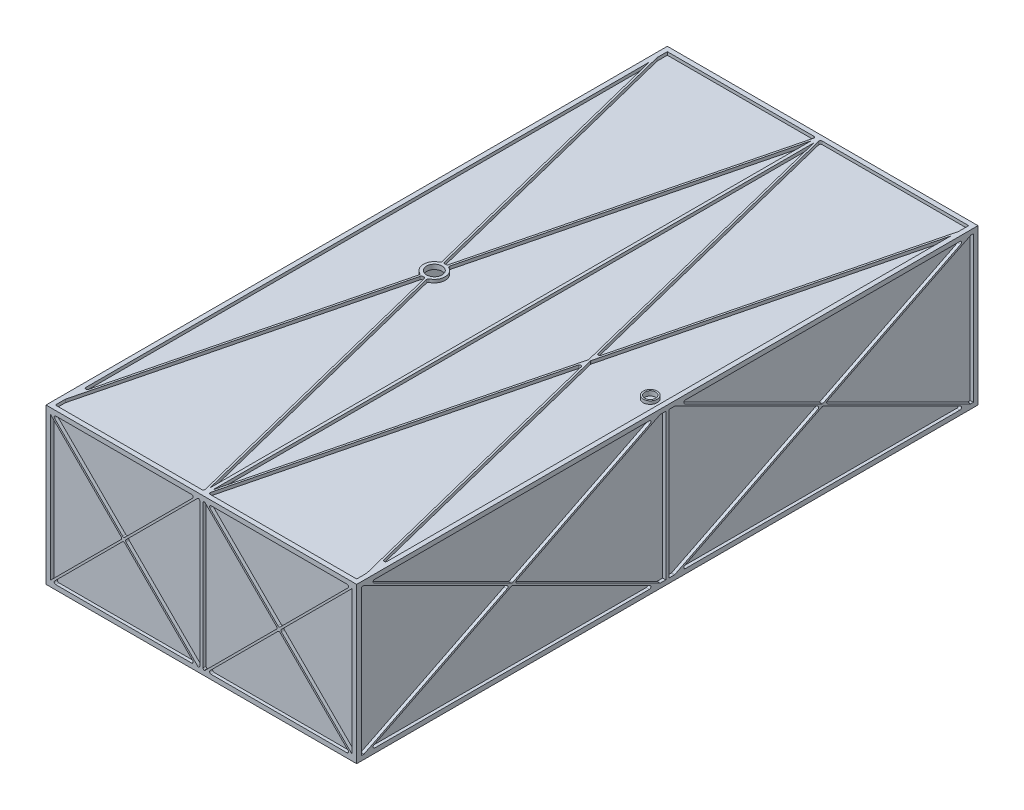
SolidWorks part; units mm, degrees
ref_plane "Front Plane" through (0, 0, 0) normal (0, 0, 1) x (1, 0, 0)
ref_plane "Top Plane" through (0, 0, 0) normal (0, 1, 0) x (1, 0, 0)
ref_plane "Right Plane" through (0, 0, 0) normal (1, 0, 0) x (0, 0, -1)
sketch "Sketch1" plane through (0, 0, 0) normal (0, 1, 0) x (1, 0, 0)
  line L1 (-500, 1000) -> (500, 1000)
  line L2 (-500, 1000) -> (-500, -1000)
  line L3 (-500, -1000) -> (500, -1000)
  line L4 (500, 1000) -> (500, -1000)
  line L5 (-500, 1000) -> (500, -1000) construction
  line L6 (-500, -1000) -> (500, 1000) construction
  point P0 (0, 0)
  dimension "D1" = 2000
  dimension "D2" = 1000
extrude "Boss-Extrude1" add sketch "Sketch1" along normal blind 500
sketch "Sketch2" plane through (0, 0, 1000) normal (0, 0, 1) x (1, 0, 0)
  line L0 (485, 485) -> (-485, 485)
  line L1 (-485, 485) -> (-485, 15)
  line L2 (-485, 15) -> (485, 15)
  line L3 (485, 15) -> (485, 485)
  line L4 (-500, 0) -> (500, 0)
  line L5 (500, 0) -> (500, 500)
  line L6 (500, 500) -> (-500, 500)
  line L7 (-500, 500) -> (-500, 0)
  line L8 (-500, 0) -> (500, 0) construction
  line L9 (500, 0) -> (500, 500) construction
  line L10 (500, 500) -> (-500, 500) construction
  line L11 (-500, 500) -> (-500, 0) construction
  dimension "D1" = 0
  dimension "D2" = 15
extrude "Cut-Extrude1" cut sketch "Sketch2" against normal through all contours L0 L1 L2 L3
sketch "Sketch3" plane through (-500, 0, 0) normal (-1, 0, 0) x (0, 0, 1)
  line L0 (-985, 15) -> (985, 15)
  line L1 (985, 15) -> (985, 485)
  line L2 (985, 485) -> (-985, 485)
  line L3 (-985, 485) -> (-985, 15)
  line L4 (-1000, 0) -> (1000, 0)
  line L5 (1000, 0) -> (1000, 500)
  line L6 (1000, 500) -> (-1000, 500)
  line L7 (-1000, 500) -> (-1000, 0)
  line L8 (-1000, 0) -> (1000, 0) construction
  line L9 (1000, 0) -> (1000, 500) construction
  line L10 (1000, 500) -> (-1000, 500) construction
  line L11 (-1000, 500) -> (-1000, 0) construction
  dimension "D1" = 0
  dimension "D2" = 15
extrude "Cut-Extrude2" cut sketch "Sketch3" against normal through all
sketch "Sketch4" plane through (0, 500, 0) normal (0, 1, 0) x (1, 0, 0)
  line L0 (485, -985) -> (485, 985)
  line L1 (485, 985) -> (-485, 985)
  line L2 (-485, 985) -> (-485, -985)
  line L3 (-485, -985) -> (485, -985)
  line L4 (500, -1000) -> (500, 1000)
  line L5 (500, 1000) -> (-500, 1000)
  line L6 (-500, 1000) -> (-500, -1000)
  line L7 (-500, -1000) -> (500, -1000)
  line L8 (500, -1000) -> (500, 1000) construction
  line L9 (500, 1000) -> (-500, 1000) construction
  line L10 (-500, 1000) -> (-500, -1000) construction
  line L11 (-500, -1000) -> (500, -1000) construction
  dimension "D1" = 0
  dimension "D2" = 15
extrude "Cut-Extrude3" cut sketch "Sketch4" against normal through all
sketch "Sketch8" plane through (0, 485, 0) normal (0, -1, 0) x (1, 0, 0)
  line L0 (485, 985) -> (485, -985) construction
  line L1 (485, -985) -> (-485, -985) construction
  line L2 (-485, -985) -> (-485, 985) construction
  line L3 (-485, 985) -> (485, 985) construction
  line L4 (485, 985) -> (485, -985)
  line L5 (485, -985) -> (-485, -985)
  line L6 (-485, -985) -> (-485, 985)
  line L7 (-485, 985) -> (485, 985)
extrude "Boss-Extrude3" add sketch "Sketch8" against normal blind 5
sketch "Sketch9" plane through (0, 15, 0) normal (0, 1, 0) x (1, 0, 0)
  line L0 (-485, 985) -> (485, 985) construction
  line L1 (485, 985) -> (485, -985) construction
  line L2 (-485, -985) -> (-485, 985) construction
  line L3 (485, -985) -> (-485, -985) construction
  line L4 (-485, 985) -> (485, 985)
  line L5 (485, 985) -> (485, -985)
  line L6 (-485, -985) -> (-485, 985)
  line L7 (485, -985) -> (-485, -985)
extrude "Boss-Extrude4" add sketch "Sketch9" against normal blind 5
sketch "Sketch10" plane through (0, 0, -985) normal (0, 0, 1) x (1, 0, 0)
  line L0 (485, 15) -> (485, 485) construction
  line L1 (-485, 15) -> (485, 15) construction
  line L2 (-485, 485) -> (-485, 15) construction
  line L3 (485, 485) -> (-485, 485) construction
  line L4 (485, 15) -> (485, 485)
  line L5 (-485, 15) -> (485, 15)
  line L6 (-485, 485) -> (-485, 15)
  line L7 (485, 485) -> (-485, 485)
extrude "Boss-Extrude5" add sketch "Sketch10" against normal blind 5
sketch "Sketch11" plane through (0, 0, 985) normal (0, 0, -1) x (-1, 0, 0)
  line L4 (-485, 15) -> (485, 15)
  line L5 (485, 15) -> (485, 485)
  line L6 (485, 485) -> (-485, 485)
  line L7 (-485, 485) -> (-485, 15)
  line L8 (-485, 15) -> (485, 15)
  line L9 (485, 15) -> (485, 485)
  line L10 (485, 485) -> (-485, 485)
  line L11 (-485, 485) -> (-485, 15)
  dimension "D1" = 0
extrude "Boss-Extrude6" add sketch "Sketch11" against normal blind 5
sketch "Sketch12" plane through (-485, 0, 0) normal (1, 0, 0) x (0, 0, -1)
  line L0 (985, 485) -> (985, 15) construction
  line L1 (985, 15) -> (-985, 15) construction
  line L2 (-985, 15) -> (-985, 485) construction
  line L3 (-985, 485) -> (985, 485) construction
  line L4 (985, 485) -> (985, 15)
  line L5 (985, 15) -> (-985, 15)
  line L6 (-985, 15) -> (-985, 485)
  line L7 (-985, 485) -> (985, 485)
extrude "Boss-Extrude7" add sketch "Sketch12" against normal blind 5
sketch "Sketch13" plane through (485, 0, 0) normal (-1, 0, 0) x (0, 0, 1)
  line L4 (985, 485) -> (-985, 485)
  line L5 (-985, 485) -> (-985, 15)
  line L6 (-985, 15) -> (985, 15)
  line L7 (985, 15) -> (985, 485)
  line L8 (985, 485) -> (-985, 485)
  line L9 (-985, 485) -> (-985, 15)
  line L10 (-985, 15) -> (985, 15)
  line L11 (985, 15) -> (985, 485)
  dimension "D1" = 0
extrude "Boss-Extrude8" add sketch "Sketch13" against normal blind 5
sketch "Sketch14" plane through (0, 0, -990) normal (0, 0, -1) x (-1, 0, 0)
  line L0 (-500, 500) -> (0, 0) construction
  line L1 (0, 0) -> (500, 500) construction
  line L2 (-500, 0) -> (0, 500) construction
  line L3 (0, 500) -> (500, 0) construction
  line L4 (-500, 0) -> (500, 0)
  line L5 (500, 0) -> (500, 500)
  line L6 (500, 500) -> (-500, 500)
  line L7 (-500, 500) -> (-500, 0)
  line L8 (-500, 0) -> (500, 0) construction
  line L9 (500, 0) -> (500, 500) construction
  line L10 (500, 500) -> (-500, 500) construction
  line L11 (-500, 500) -> (-500, 0) construction
  line L12 (-495.7574, 0) -> (-250, 245.7574)
  line L13 (5, 490.7574) -> (245.7574, 250)
  line L14 (-500, 495.7574) -> (-254.2426, 250)
  line L15 (4.2426, 0) -> (250, 245.7574)
  line L16 (-500, 4.2426) -> (-254.2426, 250)
  line L17 (4.2426, 500) -> (250, 254.2426)
  line L18 (-495.7574, 500) -> (-250, 254.2426)
  line L19 (5, 9.2426) -> (245.7574, 250)
  line L20 (-497.8787, 502.1213) -> (0, 4.2426) construction
  line L21 (-502.1213, 497.8787) -> (0, -4.2426) construction
  line L22 (-502.1213, 2.1213) -> (0, 504.2426) construction
  line L23 (-497.8787, -2.1213) -> (0, 495.7574) construction
  line L24 (0, -4.2426) -> (502.1213, 497.8787) construction
  line L25 (0, 504.2426) -> (502.1213, 2.1213) construction
  line L26 (0, 495.7574) -> (497.8787, -2.1213) construction
  line L27 (0, 4.2426) -> (497.8787, 502.1213) construction
  line L28 (-250, 254.2426) -> (-4.2426, 500)
  line L29 (-245.7574, 250) -> (-5, 490.7574)
  line L30 (-250, 245.7574) -> (-4.2426, 0)
  line L31 (-245.7574, 250) -> (-5, 9.2426)
  line L32 (250, 254.2426) -> (495.7574, 500)
  line L33 (254.2426, 250) -> (500, 495.7574)
  line L34 (254.2426, 250) -> (500, 4.2426)
  line L35 (250, 245.7574) -> (495.7574, 0)
  line L36 (-500, 4.2426) -> (-500, 0)
  line L37 (-500, 0) -> (-495.7574, 0)
  line L38 (-4.2426, 0) -> (4.2426, 0)
  line L39 (495.7574, 0) -> (500, 0)
  line L40 (500, 0) -> (500, 4.2426)
  line L41 (495.7574, 500) -> (500, 500)
  line L42 (500, 500) -> (500, 495.7574)
  line L43 (4.2426, 500) -> (-4.2426, 500)
  line L44 (-495.7574, 500) -> (-500, 500)
  line L45 (-500, 500) -> (-500, 495.7574)
  line L46 (0, 495.7574) -> (0, 4.2426) construction
  line L49 (5, 490.7574) -> (5, 9.2426)
  line L51 (-5, 490.7574) -> (-5, 9.2426)
  dimension "D4" = 5
  dimension "D5" = 5
  dimension "D1" = 0
  dimension "D2" = 3
  dimension "D3" = 3
extrude "Boss-Extrude9" add sketch "Sketch14" along normal blind 10
sketch "Sketch15" plane through (490, 0, 0) normal (1, 0, 0) x (0, 0, -1)
  line L0 (-1000, 500) -> (0, 0) construction
  line L1 (0, 0) -> (1000, 500) construction
  line L2 (-1000, 0) -> (0, 500) construction
  line L3 (0, 500) -> (1000, 0) construction
  line L4 (-1000, 0) -> (1000, 0)
  line L5 (1000, 0) -> (1000, 500)
  line L6 (1000, 500) -> (-1000, 500)
  line L7 (-1000, 500) -> (-1000, 0)
  line L20 (-1000, 0) -> (1000, 0) construction
  line L21 (1000, 0) -> (1000, 500) construction
  line L22 (1000, 500) -> (-1000, 500) construction
  line L23 (-1000, 500) -> (-1000, 0) construction
  line L24 (-1000, 496.6459) -> (-506.7082, 250)
  line L25 (6.7082, 0) -> (500, 246.6459)
  line L26 (-993.2918, 0) -> (-500, 246.6459)
  line L27 (5, 494.1459) -> (493.2918, 250)
  line L47 (-993.2918, 500) -> (-500, 253.3541)
  line L48 (5, 5.8541) -> (493.2918, 250)
  line L51 (-1000, 3.3541) -> (-506.7082, 250)
  line L52 (6.7082, 500) -> (500, 253.3541)
  line L53 (-998.6584, 502.6833) -> (0, 3.3541) construction
  line L54 (-1001.3416, 497.3167) -> (0, -3.3541) construction
  line L55 (-1001.3416, 2.6833) -> (0, 503.3541) construction
  line L56 (-998.6584, -2.6833) -> (0, 496.6459) construction
  line L57 (0, -3.3541) -> (1001.3416, 497.3167) construction
  line L58 (0, 503.3541) -> (1001.3416, 2.6833) construction
  line L59 (0, 496.6459) -> (998.6584, -2.6833) construction
  line L60 (0, 3.3541) -> (998.6584, 502.6833) construction
  line L61 (-500, 253.3541) -> (-6.7082, 500)
  line L62 (-500, 246.6459) -> (-6.7082, 0)
  line L63 (-493.2918, 250) -> (-5, 5.8541)
  line L64 (-493.2918, 250) -> (-5, 494.1459)
  line L65 (500, 253.3541) -> (993.2918, 500)
  line L66 (500, 246.6459) -> (993.2918, 0)
  line L67 (506.7082, 250) -> (1000, 496.6459)
  line L68 (506.7082, 250) -> (1000, 3.3541)
  line L69 (0, 500) -> (0, 0) construction
  line L70 (-5, 494.1459) -> (-5, 5.8541)
  line L71 (-6.7082, 0) -> (6.7082, 0)
  line L72 (-5, 500) -> (-5, 0) construction
  line L73 (5, 494.1459) -> (5, 5.8541)
  line L74 (1000, 3.3541) -> (1000, 0)
  line L75 (1000, 0) -> (993.2918, 0)
  line L76 (993.2918, 500) -> (1000, 500)
  line L77 (1000, 500) -> (1000, 496.6459)
  line L78 (-6.7082, 500) -> (6.7082, 500)
  line L79 (-993.2918, 500) -> (-1000, 500)
  line L80 (-1000, 500) -> (-1000, 496.6459)
  line L81 (-1000, 3.3541) -> (-1000, 0)
  line L82 (-1000, 0) -> (-993.2918, 0)
  dimension "D4" = 5
  dimension "D5" = 5
  dimension "D1" = 0
  dimension "D2" = 3
  dimension "D3" = 3
extrude "Boss-Extrude10" add sketch "Sketch15" along normal blind 10
sketch "Sketch16" plane through (0, 490, 0) normal (0, 1, 0) x (1, 0, 0)
  line L0 (500, 1000) -> (0, -1000) construction
  line L1 (0, -1000) -> (-500, 1000) construction
  line L2 (-500, -1000) -> (0, 1000) construction
  line L3 (0, 1000) -> (500, -1000) construction
  line L4 (-500, 1000) -> (-500, -1000)
  line L5 (-500, -1000) -> (500, -1000)
  line L6 (500, -1000) -> (500, 1000)
  line L7 (500, 1000) -> (-500, 1000)
  line L8 (-500, 1000) -> (-500, -1000) construction
  line L9 (-500, -1000) -> (500, -1000) construction
  line L10 (500, -1000) -> (500, 1000) construction
  line L11 (500, 1000) -> (-500, 1000) construction
  line L12 (496.9077, 1000) -> (250, 12.3693)
  line L13 (-5, -967.6307) -> (-238.6321, -33.1024)
  line L14 (-496.9077, -1000) -> (-255.5471, -34.5576)
  line L15 (5, 967.6307) -> (246.9077, 0)
  line L16 (500, 987.6307) -> (253.0923, 0)
  line L17 (-3.0923, -1000) -> (-244.4529, -34.5576)
  line L18 (-500, -987.6307) -> (-261.3679, -33.1024)
  line L19 (3.0923, 1000) -> (250, 12.3693)
  line L20 (0, -987.6307) -> (-497.0896, 1000.7276) construction
  line L21 (0, -1012.3693) -> (-502.9104, 999.2724) construction
  line L22 (-496.9077, 1000) -> (-500, 1000)
  line L23 (-500, 1000) -> (-500, 987.6307)
  line L24 (-502.9104, -999.2724) -> (0, 1012.3693) construction
  line L25 (0, 1012.3693) -> (502.9104, -999.2724) construction
  line L26 (497.0896, 1000.7276) -> (0, -987.6307) construction
  line L27 (502.9104, 999.2724) -> (0, -1012.3693) construction
  line L28 (0, 987.6307) -> (497.0896, -1000.7276) construction
  line L29 (-497.0896, -1000.7276) -> (0, 987.6307) construction
  line L30 (-500, -987.6307) -> (-500, -1000)
  line L31 (-500, -1000) -> (-496.9077, -1000)
  line L32 (-3.0923, -1000) -> (3.0923, -1000)
  line L33 (500, -987.6307) -> (500, -1000)
  line L34 (500, -1000) -> (496.9077, -1000)
  line L35 (496.9077, 1000) -> (500, 1000)
  line L36 (500, 1000) -> (500, 987.6307)
  line L37 (-3.0923, 1000) -> (3.0923, 1000)
  line L38 (246.9077, 0) -> (5, -967.6307)
  line L39 (253.0923, 0) -> (500, -987.6307)
  line L40 (250, -12.3693) -> (496.9077, -1000)
  line L41 (250, -12.3693) -> (3.0923, -1000)
  line L42 (-244.4529, 34.5576) -> (-3.0923, 1000)
  line L43 (-261.3679, 33.1024) -> (-500, 987.6307)
  line L44 (-238.6321, 33.1024) -> (-5, 967.6307)
  line L45 (-255.5471, 34.5576) -> (-496.9077, 1000)
  line L46 (0, 987.6307) -> (0, -987.6307) construction
  line L47 (5, 987.6307) -> (5, -987.6307) construction
  line L48 (5, 967.6307) -> (5, -967.6307)
  line L49 (-5, 967.6307) -> (-5, -967.6307)
  line L50 (485, -985) -> (485, 985) construction
  circle A1 centre (-250, 0) radius 25
  arc A2 (-244.4529, 34.5576) -> (-255.5471, 34.5576) centre (-250, 0) ccw
  arc A3 (-261.3679, 33.1024) -> (-261.3679, -33.1024) centre (-250, 0) ccw
  arc A4 (-255.5471, -34.5576) -> (-244.4529, -34.5576) centre (-250, 0) ccw
  arc A5 (-238.6321, -33.1024) -> (-238.6321, 33.1024) centre (-250, 0) ccw
  circle A6 centre (445, 0) radius 17.5
  circle A7 centre (445, 0) radius 22.5
  point P48 (-250, 0)
  dimension "D7" = 70
  dimension "D6" = 50
  dimension "D8" = 35
  dimension "D4" = 5
  dimension "D10" = 40
  dimension "D1" = 0
  dimension "D2" = 3
  dimension "D3" = 3
  dimension "D5" = 5
  dimension "D9" = 5
extrude "Boss-Extrude11" add sketch "Sketch16" along normal blind 10
fillet "Fillet2" radius 5 24 edges at (10.7574, 485, -995) (5, 485, -995) (19.2426, 485, -995) (254.2426, 250, -995) (245.7574, 250, -995) (250, 254.2426, -995) (480.7574, 15, -995) (19.2426, 15, -995) (10.7574, 15, -995) (5, 15, -995) (250, 245.7574, -995) (480.7574, 485, -995) (-19.2426, 15, -995) (-5, 15, -995) (-10.7574, 15, -995) (-10.7574, 485, -995) (-5, 485, -995) (-19.2426, 485, -995) (-480.7574, 15, -995) (-480.7574, 485, -995) (-245.7574, 250, -995) (-250, 254.2426, -995) (-254.2426, 250, -995) (-250, 245.7574, -995)
fillet "Fillet5" radius 5 20 edges at (495, 253.3541, -500) (495, 253.3541, 500) (495, 485, 36.7082) (495, 250, -493.2918) (495, 250, 506.7082) (495, 485, -36.7082) (495, 485, 963.2918) (495, 250, 493.2918) (495, 250, -506.7082) (495, 15, 963.2918) (495, 15, -23.2918) (495, 15, 23.2918) (495, 15, 36.7082) (495, 15, -963.2918) (495, 246.6459, 500) (495, 246.6459, -500) (495, 485, -963.2918) (495, 485, -23.2918) (495, 485, 23.2918) (495, 15, -36.7082)
fillet "Fillet6" radius 5 18 edges at (250, 495, 12.3693) (485, 495, 927.6307) (-485, 495, 927.6307) (250, 495, -12.3693) (246.9077, 495, 0) (-6.8423, 495, -985) (6.8423, 495, -985) (253.0923, 495, 0) (6.8423, 495, 985) (-6.8423, 495, 985) (-261.3679, 495, 33.1024) (-261.3679, 495, -33.1024) (-255.5471, 495, -34.5576) (-238.6321, 495, -33.1024) (-244.4529, 495, -34.5576) (-238.6321, 495, 33.1024) (-255.5471, 495, 34.5576) (-244.4529, 495, 34.5576)
mirror "Mirror1" about plane through (0, 0, 0) normal (0, 0, 1) of "Fillet2", "Boss-Extrude9"
mirror "Mirror2" about plane through (0, 0, 0) normal (1, 0, 0) of "Fillet5", "Boss-Extrude10"
pattern_linear "LPattern1" count 2 spacing 490 along (0, -1, 0) of "Boss-Extrude11", "Fillet6"
sketch "Sketch17" plane through (0, 0, 0) normal (1, 0, 0) x (0, 0, -1)
  line L8 (-1000, 500) -> (0, 0) construction
  line L9 (0, 0) -> (1000, 500) construction
  line L10 (1000, 0) -> (0, 500) construction
  line L11 (0, 500) -> (-1000, 0) construction
  line L152 (-1000, 0) -> (1000, 0)
  line L153 (1000, 0) -> (1000, 500)
  line L154 (1000, 500) -> (-1000, 500)
  line L155 (-1000, 500) -> (-1000, 0)
  line L156 (-1000, 0) -> (1000, 0) construction
  line L157 (1000, 0) -> (1000, 500) construction
  line L158 (1000, 500) -> (-1000, 500) construction
  line L159 (-1000, 500) -> (-1000, 0) construction
  line L160 (-1000, 496.6459) -> (-506.7082, 250)
  line L161 (6.7082, 0) -> (500, 246.6459)
  line L162 (1000, 3.3541) -> (506.7082, 250)
  line L163 (-6.7082, 500) -> (-500, 253.3541)
  line L164 (-993.2918, 500) -> (-500, 253.3541)
  line L165 (5, 5.8541) -> (493.2918, 250)
  line L166 (993.2918, 0) -> (500, 246.6459)
  line L167 (-5, 494.1459) -> (-493.2918, 250)
  line L168 (-1001.3416, 497.3167) -> (0, -3.3541) construction
  line L169 (0, -3.3541) -> (1001.3416, 497.3167) construction
  line L170 (0, 503.3541) -> (-1001.3416, 2.6833) construction
  line L171 (1001.3416, 2.6833) -> (0, 503.3541) construction
  line L172 (0, 3.3541) -> (998.6584, 502.6833) construction
  line L173 (998.6584, -2.6833) -> (0, 496.6459) construction
  line L174 (-998.6584, 502.6833) -> (0, 3.3541) construction
  line L175 (0, 496.6459) -> (-998.6584, -2.6833) construction
  line L176 (-993.2918, 500) -> (-1000, 500)
  line L177 (-1000, 500) -> (-1000, 496.6459)
  line L178 (-1000, 3.3541) -> (-1000, 0)
  line L179 (-1000, 0) -> (-993.2918, 0)
  line L180 (1000, 3.3541) -> (1000, 0)
  line L181 (1000, 0) -> (993.2918, 0)
  line L182 (-6.7082, 0) -> (6.7082, 0)
  line L183 (-6.7082, 500) -> (6.7082, 500)
  line L184 (993.2918, 500) -> (1000, 500)
  line L185 (1000, 500) -> (1000, 496.6459)
  line L186 (500, 253.3541) -> (993.2918, 500)
  line L187 (493.2918, 250) -> (5, 494.1459)
  line L188 (500, 253.3541) -> (6.7082, 500)
  line L189 (506.7082, 250) -> (1000, 496.6459)
  line L190 (-506.7082, 250) -> (-1000, 3.3541)
  line L191 (-500, 246.6459) -> (-6.7082, 0)
  line L192 (-500, 246.6459) -> (-993.2918, 0)
  line L193 (-493.2918, 250) -> (-5, 5.8541)
  line L194 (0, 496.6459) -> (0, 3.3541) construction
  line L195 (-5, 494.1459) -> (-5, 5.8541)
  line L196 (5, 494.1459) -> (5, 5.8541)
  line L197 (-5, 496.6459) -> (-5, 3.3541) construction
  line L198 (5, 496.6459) -> (5, 3.3541) construction
  dimension "D1" = 0
  dimension "D2" = 3
  dimension "D3" = 3
  dimension "D4" = 5
  dimension "D5" = 5
extrude "Boss-Extrude12" add sketch "Sketch17" along normal mid plane 10
sketch "Sketch20" plane through (0, 500, 0) normal (0, 1, 0) x (1, 0, 0)
  circle A0 centre (445, 0) radius 17.5 construction
  circle A1 centre (-250, 0) radius 25 construction
  circle A2 centre (445, 0) radius 17.5
  circle A3 centre (-250, 0) radius 25
extrude "Cut-Extrude4" cut sketch "Sketch20" against normal through all
sketch "Sketch18" plane through (0, 0, 0) normal (0, 0, 1) x (1, 0, 0)
  line L1 (313.5, 10) -> (316.5, 10)
  line L2 (-235, 250) -> (49765, 250) construction
  line L3 (-485, 480.7574) -> (-485, 19.2426) construction
  line L4 (500, 0) -> (500, 500)
  line L5 (500, 500) -> (-500, 500)
  line L6 (-500, 500) -> (-500, 0)
  line L7 (-500, 0) -> (500, 0)
  line L8 (500, 0) -> (500, 500) construction
  line L9 (500, 500) -> (-500, 500) construction
  line L10 (-500, 500) -> (-500, 0) construction
  line L11 (-500, 0) -> (500, 0) construction
  line L12 (315, 490) -> (315, 10) construction
  line L13 (-315, 490) -> (-315, 10) construction
  line L14 (315, 160) -> (-315, 160) construction
  line L15 (-315, 90) -> (490, 90) construction
  line L16 (490, 88.5) -> (490, 91.5)
  line L17 (-313.5, 490) -> (-316.5, 490)
  line L18 (313.5, 490) -> (313.5, 161.5)
  line L20 (-316.5, 490) -> (-316.5, 158.5)
  line L22 (316.5, 490) -> (316.5, 158.5)
  line L23 (313.5, 158.5) -> (-313.5, 158.5)
  line L24 (-313.5, 490) -> (-313.5, 161.5)
  line L26 (490, 490) -> (-490, 490) construction
  line L27 (-490, 490) -> (-490, 10) construction
  line L28 (-490, 10) -> (490, 10) construction
  line L29 (490, 10) -> (490, 490) construction
  line L30 (316.5, 490) -> (313.5, 490)
  line L31 (485, 19.2426) -> (485, 480.7574) construction
  line L32 (-313.5, 10) -> (-316.5, 10)
  line L33 (315, 158.5) -> (-315, 158.5) construction
  line L34 (313.5, 158.5) -> (313.5, 10)
  line L35 (316.5, 161.5) -> (316.5, 91.5)
  line L36 (316.5, 490) -> (316.5, 10) construction
  line L37 (-316.5, 161.5) -> (-316.5, 10)
  line L38 (-316.5, 490) -> (-316.5, 10) construction
  line L39 (-313.5, 91.5) -> (-313.5, 88.5)
  line L40 (-313.5, 88.5) -> (-313.5, 10)
  line L41 (-313.5, 490) -> (-313.5, 10) construction
  line L42 (313.5, 161.5) -> (-313.5, 161.5)
  line L43 (-313.5, 158.5) -> (-313.5, 91.5)
  line L44 (316.5, 91.5) -> (490, 91.5)
  line L45 (316.5, 88.5) -> (316.5, 10)
  line L46 (316.5, 88.5) -> (490, 88.5)
  line L47 (313.5, 490) -> (313.5, 10) construction
  point P12 (-485, 250)
  dimension "D2" = 10
  dimension "D3" = 800
  dimension "D4" = 800
  dimension "D5" = 80
  dimension "D6" = 150
  dimension "D7" = 1.5
  dimension "D9" = 630
  dimension "D10" = 1.5
  dimension "D11" = 1.5
  dimension "D12" = 1.5
  dimension "D1" = 0
  dimension "D8" = 1.5
